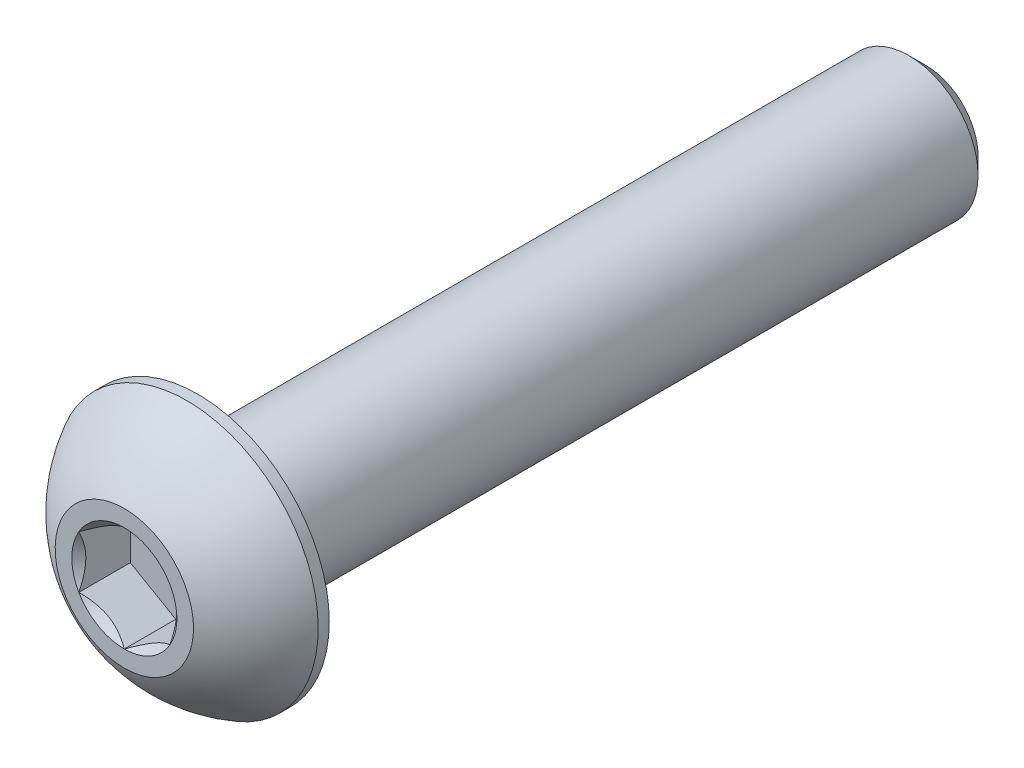
SolidWorks part; units mm, degrees
ref_plane "Front" through (0, 0, 0) normal (0, 0, 1) x (1, 0, 0)
ref_plane "Top" through (0, 0, 0) normal (0, 1, 0) x (1, 0, 0)
ref_plane "Right" through (0, 0, 0) normal (1, 0, 0) x (0, 0, -1)
sketch "Sketch1" plane through (0, 0, 0) normal (1, 0, 0) x (0, 0, -1)
  line L2 (2.5654, 2.413) -> (27.9654, 2.413)
  line L3 (27.9654, 2.413) -> (27.9654, 0)
  line L4 (27.9654, 0) -> (2.5654, 0)
  line L6 (2.1806, 4.5847) -> (2.5654, 4.5847) construction
  line L7 (27.9654, 2.413) -> (27.9654, -2.413) construction
  line L8 (0, 0) -> (2.5654, 0) construction
  line L9 (2.5654, 4.5847) -> (2.5654, -4.5847) construction
  line L11 (2.5654, 2.413) -> (2.5654, 0)
  line L13 (0, 1.5875) -> (0, -1.5875) construction
  line L14 (0, 1.5875) -> (0, 2.413) construction
  arc A3 (0, 2.413) -> (2.1806, 4.5847) centre (4.5749, 0) cw construction
  dimension "D1" = 0.3848
revolve "Revolve1" add sketch "Sketch1" angle 360 mid plane about L4
sketch "Sketch3" plane through (0, 0, -27.9654) normal (0, 0, -1) x (-1, 0, 0)
  circle A0 centre (0, 0) radius 2.413
curve "Helix/Spiral1" [suppressed]
sketch "Sketch2" plane through (0, 0, 0) normal (1, 0, 0) x (0, 0, -1)
  line L0 (27.9654, 2.413) -> (28.6599, 2.413)
  line L1 (28.6599, 2.413) -> (28.3623, 1.8974)
  line L2 (28.3623, 1.8974) -> (28.2631, 1.8974)
  line L3 (28.2631, 1.8974) -> (27.9654, 2.413)
  line L4 (28.1142, 2.1552) -> (28.5111, 2.1552) construction
  dimension "D1" = 60
  dimension "D2" = 0.0992
  dimension "D3" = 0.3969
chamfer "Chamfer1" distance 0.5953 angle 45 1 edges at (0, 2.413, -27.9654)
sweep "Cut-Sweep1" [suppressed] cut profiles "Sketch2" path "Helix/Spiral1"
sketch "Sketch7" plane through (0, 0, 0) normal (1, 0, 0) x (0, 0, -1)
  line L6 (2.1806, 4.5847) -> (2.5654, 4.5847) construction
  line L8 (0, 0) -> (2.5654, 0) construction
  line L11 (2.5654, 4.5847) -> (2.5654, -4.5847) construction
  line L12 (2.1806, 4.5847) -> (2.5654, 4.5847)
  line L13 (0, 0) -> (2.5654, 0)
  line L14 (0, 1.5875) -> (0, -1.5875) construction
  line L15 (2.5654, 4.5847) -> (2.5654, 0)
  line L16 (0, 2.413) -> (0, 0)
  arc A2 (2.1806, 4.5847) -> (0, 2.413) centre (4.5749, 0) ccw construction
  arc A3 (2.1806, 4.5847) -> (0, 2.413) centre (4.5749, 0) ccw
revolve "Revolve2" add sketch "Sketch7" angle 360 mid plane about L13
sketch "Sketch5" plane through (0, 0, 0) normal (0, 0, 1) x (1, 0, 0)
  line L1 (1.5875, -0.9165) -> (1.5875, 0.9165)
  line L2 (1.5875, 0.9165) -> (0, 1.8331)
  line L3 (0, 1.8331) -> (-1.5875, 0.9165)
  line L4 (-1.5875, 0.9165) -> (-1.5875, -0.9165)
  line L5 (-1.5875, -0.9165) -> (0, -1.8331)
  line L6 (0, -1.8331) -> (1.5875, -0.9165)
  circle A0 centre (0, 0) radius 1.5875 construction
extrude "Cut-Extrude2" cut sketch "Sketch5" against normal blind 1.7958
sketch "Sketch6" plane through (0, 0, 0) normal (0, 0, 1) x (1, 0, 0)
  circle A0 centre (0, 0) radius 1.8331
extrude "Cut-Extrude3" cut sketch "Sketch6" against normal blind 1.7958 draft 45
sketch "Sketch9" [suppressed] plane through (0, 0, -2.5654) normal (0, 0, 1) x (1, 0, 0)
  circle A2 centre (0, 0) radius 2.413
extrude "Boss-Extrude2" [suppressed] add sketch "Sketch9" against normal offset from surface (28.575 mm away) 31.75 up to face at (0, 1.8177, -27.9654)
sketch "Sketch10" plane through (0, 0, 0) normal (1, 0, 0) x (0, 0, -1)
  line L0 (27.9654, 2.413) -> (27.9654, -2.413) construction
  point P0 (26.7748, -2.413)
  dimension "D1" = 1.1906
equation "\"D3@Helix/Spiral1\" = \"Lg@Sketch1\" + \"D4@Helix/Spiral1\""
equation "\"D2@Sketch2\" = \"D4@Helix/Spiral1\" * .125"
equation "\"D3@Sketch2\" = \"D4@Helix/Spiral1\" * .5"
equation "\"D1@Chamfer1\" = \"D4@Helix/Spiral1\" * .75"
equation "\"D1@Cut-Extrude2\" = \"Head Ht@Sketch1\" * .7"
equation "\"D1@Sketch1\" = \"Head Ht@Sketch1\" * .15"
equation "\"D1@Sketch10\" = \"D4@Helix/Spiral1\" * 1.5"
equation "\"D1@Cut-Extrude3\" = \"D1@Cut-Extrude2\""
